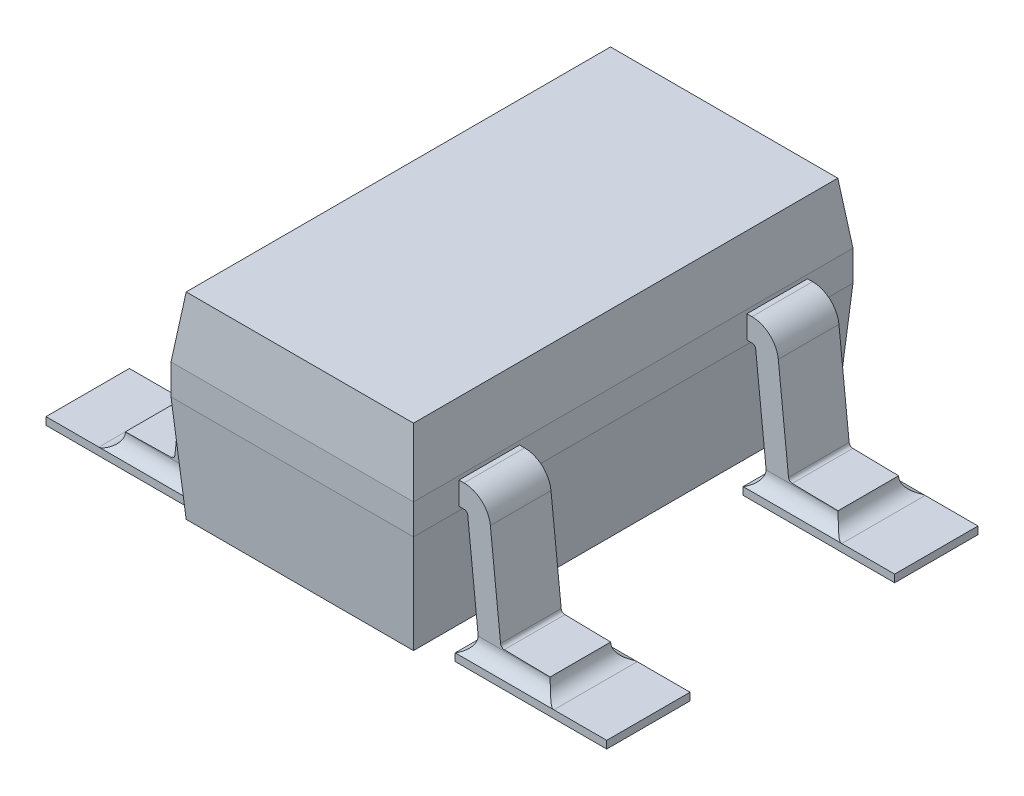
SolidWorks part; units mm, degrees
ref_plane "Front Plane" through (0, 0, 0) normal (0, 0, 1) x (1, 0, 0)
ref_plane "Top Plane" through (0, 0, 0) normal (0, 1, 0) x (1, 0, 0)
ref_plane "Right Plane" through (0, 0, 0) normal (1, 0, 0) x (0, 0, -1)
ref_plane "Plane1" through (0, 0, 0) normal (0, 0, 1) x (1, 0, 0)
ref_plane "Plane5" through (0, 0, 0.95) normal (0, 0, 1) x (1, 0, 0)
sketch "Sketch1" plane through (0, 0, 0) normal (0, 0, 1) x (1, 0, 0)
  line L0 (-0.75, 1.4) -> (0.75, 1.4)
  line L1 (0.75, 0.1) -> (-0.75, 0.1)
  line L3 (0, -55) -> (0, 55) construction
  line L4 (55, 0) -> (-55, 0) construction
  line L5 (-0.75, 1.4) -> (-0.8, 1)
  line L6 (-0.8, 1) -> (-0.8, 0.8)
  line L7 (-0.8, 0.8) -> (-0.75, 0.1)
  line L8 (0.75, 1.4) -> (0.8, 1)
  line L9 (0.8, 1) -> (0.8, 0.8)
  line L10 (0.8, 0.8) -> (0.75, 0.1)
  dimension "D5" = 0.2
  dimension "D1" = 1.3
  dimension "D2" = 1.6
  dimension "D3" = 0.8
  dimension "D4" = 0.1
  dimension "D6" = 1.5
  dimension "D7" = 0.75
  dimension "D8" = 0.05
  dimension "D9" = 0.8
extrude "Boss-Extrude1" add sketch "Sketch1" along normal mid plane 2.9
ref_plane "Plane2" [suppressed] through (0, 0, 4.445) normal (0, 0, 1) x (1, 0, 0)
sketch "Sketch4" plane through (0, 0, 0) normal (1, 0, 0) x (0, 0, -1)
  line L0 (-1.4, 1.4) -> (-1.45, 1)
  line L1 (-1.45, 1.4) -> (1.45, 1.4) construction
  line L2 (-1.45, 1) -> (-1.45, 0.8)
  line L3 (-1.45, 0.8) -> (-1.4, 0.1)
  line L4 (-1.45, 0.1) -> (1.45, 0.1) construction
  line L5 (-1.4, 0.1) -> (-1.6, 0.1)
  line L6 (-1.6, 0.1) -> (-1.6, 1.4)
  line L7 (-1.6, 1.4) -> (-1.4, 1.4)
  line L8 (1.45, 1) -> (1.4, 1.4)
  line L9 (1.4, 1.4) -> (1.6, 1.4)
  line L10 (1.6, 1.4) -> (1.6, 0.1)
  line L11 (1.6, 0.1) -> (1.4, 0.1)
  line L12 (1.4, 0.1) -> (1.45, 0.8)
  line L13 (1.45, 0.8) -> (1.45, 1)
  line L14 (1.45, 1) -> (1.45, 1.4) construction
  dimension "D1" = 0.05
  dimension "D2" = 0.2
  dimension "D3" = 0.2
  dimension "D4" = 0.05
extrude "Cut-Extrude2" cut sketch "Sketch4" against normal through all and the other way through all
sketch "Sketch2" plane through (0, 0, 0.95) normal (0, 0, 1) x (1, 0, 0)
  line L0 (0.9327, 0.8105) -> (1, 0.1698)
  line L1 (1.0977, 0.0803) -> (1.4, 0.075)
  line L2 (-0.9327, 0.8105) -> (-1, 0.1698)
  line L3 (-1.0977, 0.0803) -> (-1.4, 0.075)
  line L4 (0.8332, 0.9) -> (-0.8332, 0.9)
  line L9 (-0.75, 0.1) -> (0.75, 0.1) construction
  line L10 (0.88, 0) -> (-0.88, 0) construction
  line L11 (0, -0.715) -> (0, 0.715) construction
  arc A0 (0.9327, 0.8105) -> (0.8332, 0.9) centre (0.8332, 0.8) ccw
  arc A1 (1, 0.1698) -> (1.0977, 0.0803) centre (1.0995, 0.1803) ccw
  arc A2 (-0.8332, 0.9) -> (-0.9327, 0.8105) centre (-0.8332, 0.8) ccw
  arc A3 (-1.0977, 0.0803) -> (-1, 0.1698) centre (-1.0995, 0.1803) ccw
  dimension "D8" = 0.1
  dimension "D1" = 2.8
  dimension "D2" = 6
  dimension "D3" = 1
  dimension "D4" = 0.9
  dimension "D5" = 0.8
  dimension "D6" = 6
  dimension "D7" = 1
  dimension "D9" = 1.4
  dimension "D10" = 0.4
  dimension "D11" = 0.4
  dimension "D12" = 0.075
  dimension "D13" = 0.075
extrude "Extrude-Thin1" add sketch "Sketch2" along normal mid plane 0.4 thin thin type mid plane wall 0.15
ref_axis "Axis1" through (0, 0, 5.61) along (0, 0, -1)
sketch "Sketch5" plane through (0, 0, 0) normal (0, 1, 0) x (1, 0, 0)
  line L2 (-1.85, -0.675) -> (-0.85, -0.675)
  line L3 (-1.85, -0.675) -> (-1.85, -1.225)
  line L4 (-1.85, -1.225) -> (-0.85, -1.225)
  line L5 (-0.85, -0.675) -> (-0.85, -1.225)
  line L6 (0.85, -0.675) -> (1.85, -0.675)
  line L8 (0.85, -0.675) -> (0.85, -1.225)
  line L9 (0.85, -1.225) -> (1.85, -1.225)
  line L10 (1.85, -0.675) -> (1.85, -1.225)
  dimension "D1" = 0.55
  dimension "D2" = 1
  dimension "D3" = 1.85
  dimension "D4" = 1.85
  dimension "D5" = 0.675
extrude "Boss-Extrude2" add sketch "Sketch5" along normal blind 0.05
fillet "Fillet1" radius 0.1 8 edges at (1.3996, 0.05, 0.95) (1.1911, 0.05, 0.75) (-1.1911, 0.05, 0.75) (0.9826, 0.05, 0.95) (-0.9826, 0.05, 0.95) (-1.3996, 0.05, 0.95) (-1.1911, 0.05, 1.15) (1.1911, 0.05, 1.15)
pattern_linear "LPattern1" count 3 spacing 0.95 along (0, 0, -1) of "Extrude-Thin1", "Boss-Extrude2", "Fillet1"
sketch "Sketch6" plane through (0, 0, 0) normal (0, 1, 0) x (1, 0, 0)
  line L0 (0.8, -1.45) -> (0.8, 1.45) construction
  line L1 (0.8, 0.5) -> (2, 0.5)
  line L2 (0.8, 0.5) -> (0.8, -0.5)
  line L3 (0.8, -0.5) -> (2, -0.5)
  line L4 (2, 0.5) -> (2, -0.5)
  dimension "D1" = 1
  dimension "D2" = 0.5
  dimension "D3" = 2
extrude "Cut-Extrude3" cut sketch "Sketch6" along normal blind 10
